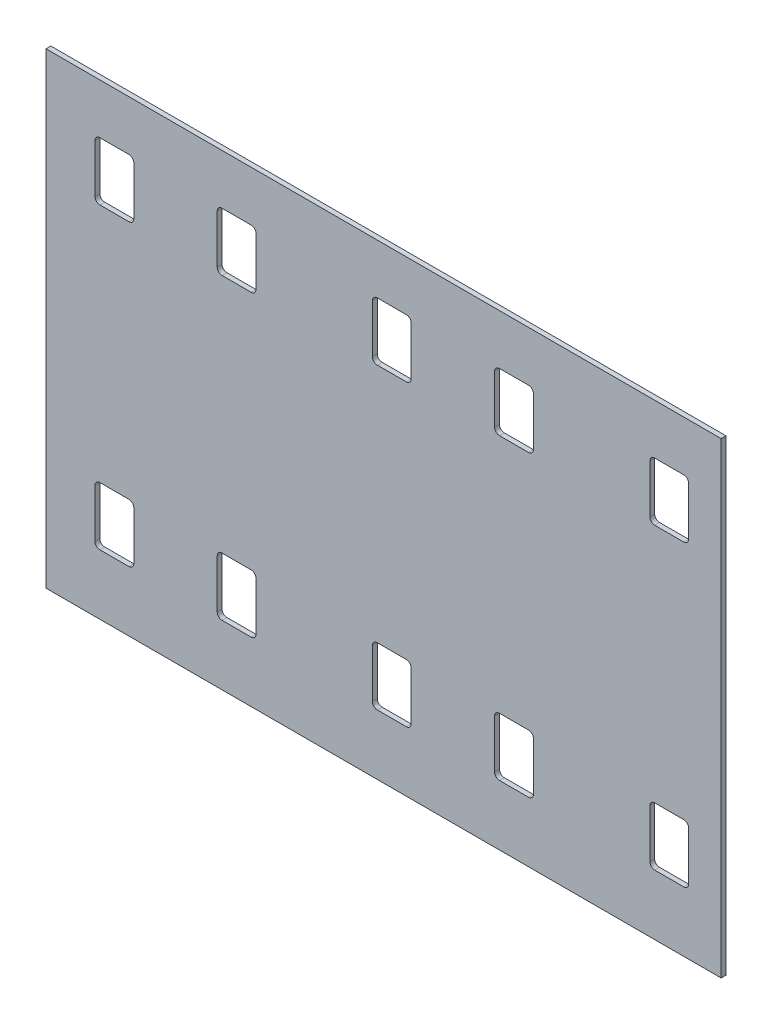
SolidWorks part; units mm, degrees
material "PP Film"
ref_plane "X-Y Datum" through (0, 0, 0) normal (0, 0, 1) x (1, 0, 0)
ref_plane "X-Z Datum" through (0, 0, 0) normal (0, 1, 0) x (1, 0, 0)
ref_plane "Y-Z Datum" through (0, 0, 0) normal (1, 0, 0) x (0, 0, -1)
sketch "Sketch1" plane through (0, 0, 0) normal (0, 0, 1) x (1, 0, 0)
  line L44 (-220.9897, 149.5877) -> (-220.9897, -156.2291)
  line L45 (-220.9897, -156.2291) -> (220.9897, -156.2291)
  line L46 (220.9897, -156.2291) -> (220.9897, 149.5877)
  line L47 (220.9897, 149.5877) -> (-220.9897, 149.5877)
  line L48 (-220.9897, 149.5877) -> (-220.9897, -156.2291)
  line L49 (-220.9897, -156.2291) -> (220.9897, -156.2291)
  line L50 (220.9897, -156.2291) -> (220.9897, 149.5877)
  line L51 (220.9897, 149.5877) -> (-220.9897, 149.5877)
  dimension "D1" = 0
extrude "Boss-Extrude1" add sketch "Sketch1" along normal blind 3.175 contours L50 L51 L48 L49
sketch "Sketch2" plane through (0, 0, 3.175) normal (0, 0, 1) x (1, 0, 0)
  line L0 (-185.7466, 116.8) -> (-166.6966, 116.8) construction
  line L1 (-185.7466, 78.7) -> (-166.6966, 78.7) construction
  line L2 (-188.9216, 113.625) -> (-188.9216, 81.875) construction
  line L3 (-163.5216, 113.625) -> (-163.5216, 81.875) construction
  line L4 (-185.7466, 116.8) -> (-166.6966, 116.8)
  line L5 (-185.7466, 78.7) -> (-166.6966, 78.7)
  line L6 (-188.9216, 113.625) -> (-188.9216, 81.875)
  line L7 (-163.5216, 113.625) -> (-163.5216, 81.875)
  line L8 (-185.7466, -78.7) -> (-166.6966, -78.7) construction
  line L9 (-188.9216, -81.875) -> (-188.9216, -113.625) construction
  line L10 (-185.7466, -116.8) -> (-166.6966, -116.8) construction
  line L11 (-163.5216, -81.875) -> (-163.5216, -113.625) construction
  line L12 (-185.7466, -78.7) -> (-166.6966, -78.7)
  line L13 (-188.9216, -81.875) -> (-188.9216, -113.625)
  line L14 (-185.7466, -116.8) -> (-166.6966, -116.8)
  line L15 (-163.5216, -81.875) -> (-163.5216, -113.625)
  line L16 (-86.6814, -78.7) -> (-105.7314, -78.7) construction
  line L17 (-83.5064, -113.625) -> (-83.5064, -81.875) construction
  line L18 (-105.7314, -116.8) -> (-86.6814, -116.8) construction
  line L19 (-108.9064, -81.875) -> (-108.9064, -113.625) construction
  line L20 (-86.6814, -78.7) -> (-105.7314, -78.7)
  line L21 (-83.5064, -113.625) -> (-83.5064, -81.875)
  line L22 (-105.7314, -116.8) -> (-86.6814, -116.8)
  line L23 (-108.9064, -81.875) -> (-108.9064, -113.625)
  line L24 (-86.6814, 116.8) -> (-105.7314, 116.8) construction
  line L25 (-83.5064, 81.875) -> (-83.5064, 113.625) construction
  line L26 (-108.9064, 113.625) -> (-108.9064, 81.875) construction
  line L27 (-105.7314, 78.7) -> (-86.6814, 78.7) construction
  line L28 (-86.6814, 116.8) -> (-105.7314, 116.8)
  line L29 (-83.5064, 81.875) -> (-83.5064, 113.625)
  line L30 (-108.9064, 113.625) -> (-108.9064, 81.875)
  line L31 (-105.7314, 78.7) -> (-86.6814, 78.7)
  arc A0 (-188.9216, 81.875) -> (-185.7466, 78.7) centre (-185.7466, 81.875) ccw construction
  arc A1 (-185.7466, 116.8) -> (-188.9216, 113.625) centre (-185.7466, 113.625) ccw construction
  arc A2 (-163.5216, 113.625) -> (-166.6966, 116.8) centre (-166.6966, 113.625) ccw construction
  arc A3 (-166.6966, 78.7) -> (-163.5216, 81.875) centre (-166.6966, 81.875) ccw construction
  arc A4 (-188.9216, 81.875) -> (-185.7466, 78.7) centre (-185.7466, 81.875) ccw
  arc A5 (-185.7466, 116.8) -> (-188.9216, 113.625) centre (-185.7466, 113.625) ccw
  arc A6 (-163.5216, 113.625) -> (-166.6966, 116.8) centre (-166.6966, 113.625) ccw
  arc A7 (-166.6966, 78.7) -> (-163.5216, 81.875) centre (-166.6966, 81.875) ccw
  arc A8 (-163.5216, -81.875) -> (-166.6966, -78.7) centre (-166.6966, -81.875) ccw construction
  arc A9 (-185.7466, -78.7) -> (-188.9216, -81.875) centre (-185.7466, -81.875) ccw construction
  arc A10 (-188.9216, -113.625) -> (-185.7466, -116.8) centre (-185.7466, -113.625) ccw construction
  arc A11 (-166.6966, -116.8) -> (-163.5216, -113.625) centre (-166.6966, -113.625) ccw construction
  arc A12 (-163.5216, -81.875) -> (-166.6966, -78.7) centre (-166.6966, -81.875) ccw
  arc A13 (-185.7466, -78.7) -> (-188.9216, -81.875) centre (-185.7466, -81.875) ccw
  arc A14 (-188.9216, -113.625) -> (-185.7466, -116.8) centre (-185.7466, -113.625) ccw
  arc A15 (-166.6966, -116.8) -> (-163.5216, -113.625) centre (-166.6966, -113.625) ccw
  arc A16 (-105.7314, -78.7) -> (-108.9064, -81.875) centre (-105.7314, -81.875) ccw construction
  arc A17 (-83.5064, -81.875) -> (-86.6814, -78.7) centre (-86.6814, -81.875) ccw construction
  arc A18 (-86.6814, -116.8) -> (-83.5064, -113.625) centre (-86.6814, -113.625) ccw construction
  arc A19 (-108.9064, -113.625) -> (-105.7314, -116.8) centre (-105.7314, -113.625) ccw construction
  arc A20 (-105.7314, -78.7) -> (-108.9064, -81.875) centre (-105.7314, -81.875) ccw
  arc A21 (-83.5064, -81.875) -> (-86.6814, -78.7) centre (-86.6814, -81.875) ccw
  arc A22 (-86.6814, -116.8) -> (-83.5064, -113.625) centre (-86.6814, -113.625) ccw
  arc A23 (-108.9064, -113.625) -> (-105.7314, -116.8) centre (-105.7314, -113.625) ccw
  arc A24 (-105.7314, 116.8) -> (-108.9064, 113.625) centre (-105.7314, 113.625) ccw construction
  arc A25 (-83.5064, 113.625) -> (-86.6814, 116.8) centre (-86.6814, 113.625) ccw construction
  arc A26 (-108.9064, 81.875) -> (-105.7314, 78.7) centre (-105.7314, 81.875) ccw construction
  arc A27 (-86.6814, 78.7) -> (-83.5064, 81.875) centre (-86.6814, 81.875) ccw construction
  arc A28 (-105.7314, 116.8) -> (-108.9064, 113.625) centre (-105.7314, 113.625) ccw
  arc A29 (-83.5064, 113.625) -> (-86.6814, 116.8) centre (-86.6814, 113.625) ccw
  arc A30 (-108.9064, 81.875) -> (-105.7314, 78.7) centre (-105.7314, 81.875) ccw
  arc A31 (-86.6814, 78.7) -> (-83.5064, 81.875) centre (-86.6814, 81.875) ccw
extrude "Cut-Extrude1" cut sketch "Sketch2" against normal through all contours L14 A15 L15 A12 L12 A13 L13 A14 | L5 A7 L7 A6 L4 A5 L6 A4 region at (-176.2216, 97.75, 3.175) region at (-176.2216, -97.75, 3.175)
sketch "Sketch3" plane through (0, 0, 3.175) normal (0, 0, 1) x (1, 0, 0)
  line L4 (-166.6966, 116.8) -> (-185.7466, 116.8)
  line L5 (-163.5216, 81.875) -> (-163.5216, 113.625)
  line L6 (-185.7466, 78.7) -> (-166.6966, 78.7)
  line L7 (-188.9216, 113.625) -> (-188.9216, 81.875)
  line L8 (-166.6966, 116.8) -> (-185.7466, 116.8)
  line L9 (-163.5216, 81.875) -> (-163.5216, 113.625)
  line L10 (-185.7466, 78.7) -> (-166.6966, 78.7)
  line L11 (-188.9216, 113.625) -> (-188.9216, 81.875)
  line L12 (-188.9216, -81.875) -> (-188.9216, -113.625)
  line L13 (-185.7466, -116.8) -> (-166.6966, -116.8)
  line L14 (-163.5216, -113.625) -> (-163.5216, -81.875)
  line L15 (-166.6966, -78.7) -> (-185.7466, -78.7)
  line L16 (-188.9216, -81.875) -> (-188.9216, -113.625)
  line L17 (-185.7466, -116.8) -> (-166.6966, -116.8)
  line L18 (-163.5216, -113.625) -> (-163.5216, -81.875)
  line L19 (-166.6966, -78.7) -> (-185.7466, -78.7)
  line L20 (-86.6814, 116.8) -> (-105.7314, 116.8)
  line L21 (-108.9064, 113.625) -> (-108.9064, 81.875)
  line L22 (-105.7314, 78.7) -> (-86.6814, 78.7)
  line L23 (-83.5064, 81.875) -> (-83.5064, 113.625)
  line L24 (-86.6814, 116.8) -> (-105.7314, 116.8)
  line L25 (-108.9064, 113.625) -> (-108.9064, 81.875)
  line L26 (-105.7314, 78.7) -> (-86.6814, 78.7)
  line L27 (-83.5064, 81.875) -> (-83.5064, 113.625)
  line L28 (-105.7314, -116.8) -> (-86.6814, -116.8)
  line L29 (-83.5064, -113.625) -> (-83.5064, -81.875)
  line L30 (-86.6814, -78.7) -> (-105.7314, -78.7)
  line L31 (-108.9064, -81.875) -> (-108.9064, -113.625)
  line L32 (-105.7314, -116.8) -> (-86.6814, -116.8)
  line L33 (-83.5064, -113.625) -> (-83.5064, -81.875)
  line L34 (-86.6814, -78.7) -> (-105.7314, -78.7)
  line L35 (-108.9064, -81.875) -> (-108.9064, -113.625)
  arc A4 (-163.5216, 113.625) -> (-166.6966, 116.8) centre (-166.6966, 113.625) ccw
  arc A5 (-166.6966, 78.7) -> (-163.5216, 81.875) centre (-166.6966, 81.875) ccw
  arc A6 (-188.9216, 81.875) -> (-185.7466, 78.7) centre (-185.7466, 81.875) ccw
  arc A7 (-185.7466, 116.8) -> (-188.9216, 113.625) centre (-185.7466, 113.625) ccw
  arc A8 (-163.5216, 113.625) -> (-166.6966, 116.8) centre (-166.6966, 113.625) ccw
  arc A9 (-166.6966, 78.7) -> (-163.5216, 81.875) centre (-166.6966, 81.875) ccw
  arc A10 (-188.9216, 81.875) -> (-185.7466, 78.7) centre (-185.7466, 81.875) ccw
  arc A11 (-185.7466, 116.8) -> (-188.9216, 113.625) centre (-185.7466, 113.625) ccw
  arc A12 (-188.9216, -113.625) -> (-185.7466, -116.8) centre (-185.7466, -113.625) ccw
  arc A13 (-166.6966, -116.8) -> (-163.5216, -113.625) centre (-166.6966, -113.625) ccw
  arc A14 (-163.5216, -81.875) -> (-166.6966, -78.7) centre (-166.6966, -81.875) ccw
  arc A15 (-185.7466, -78.7) -> (-188.9216, -81.875) centre (-185.7466, -81.875) ccw
  arc A16 (-188.9216, -113.625) -> (-185.7466, -116.8) centre (-185.7466, -113.625) ccw
  arc A17 (-166.6966, -116.8) -> (-163.5216, -113.625) centre (-166.6966, -113.625) ccw
  arc A18 (-163.5216, -81.875) -> (-166.6966, -78.7) centre (-166.6966, -81.875) ccw
  arc A19 (-185.7466, -78.7) -> (-188.9216, -81.875) centre (-185.7466, -81.875) ccw
  arc A20 (-105.7314, 116.8) -> (-108.9064, 113.625) centre (-105.7314, 113.625) ccw
  arc A21 (-108.9064, 81.875) -> (-105.7314, 78.7) centre (-105.7314, 81.875) ccw
  arc A22 (-86.6814, 78.7) -> (-83.5064, 81.875) centre (-86.6814, 81.875) ccw
  arc A23 (-83.5064, 113.625) -> (-86.6814, 116.8) centre (-86.6814, 113.625) ccw
  arc A24 (-105.7314, 116.8) -> (-108.9064, 113.625) centre (-105.7314, 113.625) ccw
  arc A25 (-108.9064, 81.875) -> (-105.7314, 78.7) centre (-105.7314, 81.875) ccw
  arc A26 (-86.6814, 78.7) -> (-83.5064, 81.875) centre (-86.6814, 81.875) ccw
  arc A27 (-83.5064, 113.625) -> (-86.6814, 116.8) centre (-86.6814, 113.625) ccw
  arc A28 (-86.6814, -116.8) -> (-83.5064, -113.625) centre (-86.6814, -113.625) ccw
  arc A29 (-83.5064, -81.875) -> (-86.6814, -78.7) centre (-86.6814, -81.875) ccw
  arc A30 (-105.7314, -78.7) -> (-108.9064, -81.875) centre (-105.7314, -81.875) ccw
  arc A31 (-108.9064, -113.625) -> (-105.7314, -116.8) centre (-105.7314, -113.625) ccw
  arc A32 (-86.6814, -116.8) -> (-83.5064, -113.625) centre (-86.6814, -113.625) ccw
  arc A33 (-83.5064, -81.875) -> (-86.6814, -78.7) centre (-86.6814, -81.875) ccw
  arc A34 (-105.7314, -78.7) -> (-108.9064, -81.875) centre (-105.7314, -81.875) ccw
  arc A35 (-108.9064, -113.625) -> (-105.7314, -116.8) centre (-105.7314, -113.625) ccw
  dimension "D1" = 0
  dimension "D2" = 0
  dimension "D3" = 0
  dimension "D4" = 0
extrude "Cut-Extrude2" cut sketch "Sketch3" against normal through all contours L35 A35 L32 A32 L33 A33 L34 A34 | L27 A27 L24 A24 L25 A25 L26 A26 region at (-96.2064, 97.75, 3.175) region at (-96.2064, -97.75, 3.175)
pattern_linear "LPattern1" count 3 spacing 181.614 along (1, 0, 0) of "Cut-Extrude1"
pattern_linear "LPattern2" count 2 spacing 181.614 along (1, 0, 0) of "Cut-Extrude2"
